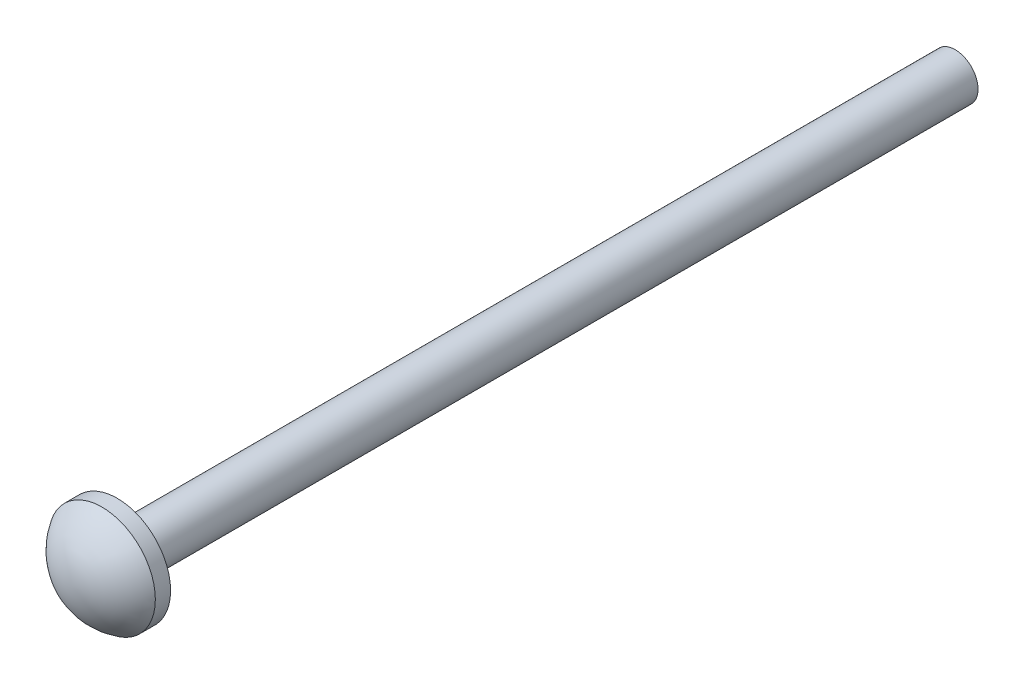
SolidWorks part; units mm, degrees
ref_plane "Front Plane" through (0, 0, 0) normal (0, 0, 1) x (1, 0, 0)
ref_plane "Top Plane" through (0, 0, 0) normal (0, 1, 0) x (1, 0, 0)
ref_plane "Right Plane" through (0, 0, 0) normal (1, 0, 0) x (0, 0, -1)
sketch "Sketch1" plane through (0, 0, 0) normal (0, 0, 1) x (1, 0, 0)
  circle A0 centre (0, 0) radius 3.5
  dimension "D1" = 7
extrude "Boss-Extrude1" add sketch "Sketch1" along normal blind 1
dome "Dome1" faces to dome 1 distance 2 reverse direction no elliptical dome no face at (3.5, 0, 1) parameters "D1"=2
sketch "Sketch3" plane through (0, 0, 0) normal (0, 0, -1) x (-1, 0, 0)
  circle A0 centre (0, 0) radius 1.5
  dimension "D1" = 3
extrude "Boss-Extrude2" add sketch "Sketch3" along normal blind 55 contours A0
sketch "Sketch4" plane through (0, 0, -55) normal (0, 0, -1) x (-1, 0, 0)
  line L0 (-1.5, 0) -> (1.5, 0) construction
  circle A0 centre (0, 0) radius 1.5 construction
  circle A1 centre (0, 0) radius 1.5 construction
ref_plane "Plane1" through (0, 0, 0) normal (0, -1, 0) x (-1, 0, 0)
